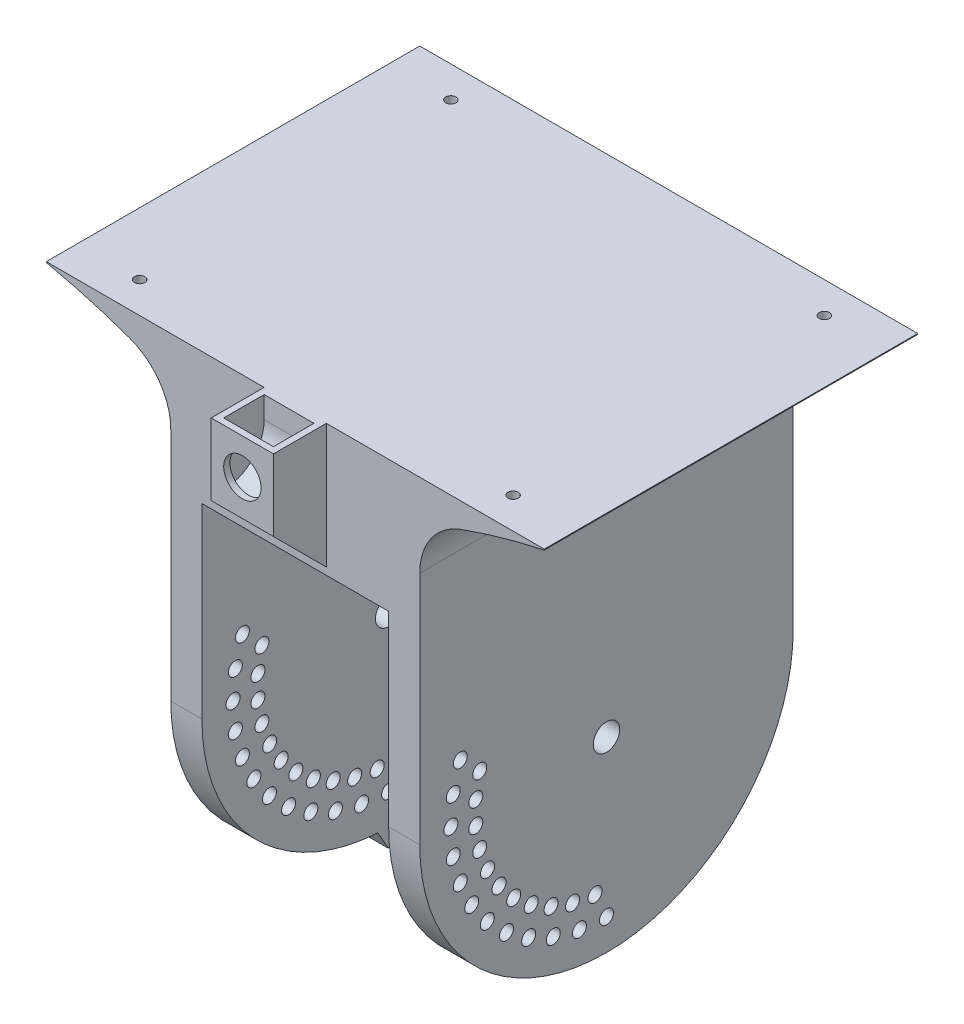
SolidWorks part; units mm, degrees
other "Markup1"
sketch "Sketch9" plane through (-80, -368.8034, 17) normal (-0.4093, -0.7365, 0.5387) x (-0.0783, -0.5598, -0.8249)
ref_plane "Front Plane" through (0, 0, 0) normal (0, 0, 1) x (1, 0, 0)
ref_plane "Top Plane" through (0, 0, 0) normal (0, 1, 0) x (1, 0, 0)
ref_plane "Right Plane" through (0, 0, 0) normal (1, 0, 0) x (0, 0, -1)
sketch "Sketch1" plane through (0, 0, 0) normal (0, 0, 1) x (1, 0, 0)
  line L0 (-10, -206.5) -> (-80, -206.5) construction
  line L1 (-10, -206.5) -> (-80, -206.5)
  line L2 (80, -206.5) -> (-80, -206.5) construction
  line L3 (80, -206.5) -> (-80, -206.5)
  line L4 (80, -206.5) -> (80, -206.7712)
  line L5 (-80, -206.5) -> (-80, -206.7712)
  arc A0 (80.2, -206.7286) -> (225.2451, -153.1407) centre (-32.1304, 320.4019) ccw construction
  arc A1 (80.2, -206.7286) -> (225.2451, -153.1407) centre (-32.1304, 320.4019) ccw
  arc A2 (-225.2451, -153.1407) -> (-80.2, -206.7286) centre (32.1304, 320.4019) ccw construction
  arc A3 (-225.2451, -153.1407) -> (-80.2, -206.7286) centre (32.1304, 320.4019) ccw
  arc A4 (80.2, -206.7286) -> (-80.2, -206.7286) centre (0, 169.6244) cw construction
  arc A5 (-80, -206.7712) -> (80, -206.7712) centre (0, 169.6244) ccw construction
  arc A6 (-80, -206.7712) -> (-51.0096, -215.1963) centre (-122.7938, -408.1138) cw
  arc A7 (80, -206.7712) -> (51.0096, -215.1963) centre (122.7938, -408.1138) ccw
  arc A8 (51.0096, -215.1963) -> (-51.0096, -215.1963) centre (0, -78.1099) cw
  point P13 (-51.0096, -215.1963)
  point P20 (0, 0)
  point P21 (0, 0)
  point P22 (0, 0)
  point P23 (-68.6071, -211.6046)
extrude "Boss-Extrude1" add sketch "Sketch1" against normal up to surface (120 mm away) contours L5 A5 L4 L3 L1 region at (0, -213.5137, 0)
sketch "Sketch2" plane through (0, 0, -120) normal (0, 0, -1) x (-1, 0, 0)
  line L1 (-40, -218.8034) -> (40, -218.8034)
  line L2 (-40, -218.8034) -> (-40, -248.8034)
  line L3 (-40, -248.8034) -> (40, -248.8034)
  line L4 (40, -218.8034) -> (40, -248.8034)
  arc A1 (-51.0096, -215.1963) -> (51.0096, -215.1963) centre (0, -78.1099) ccw construction
  point P4 (0, 0)
  point P7 (0, 0)
  point P8 (46.2922, -257.5156)
  point P9 (0, 0)
  point P13 (0, 0)
  dimension "D1" = 30
  dimension "D2" = 80
extrude "Boss-Extrude2" add sketch "Sketch2" against normal up to surface (120 mm away) up to face at (0, -210.8422, 0)
fillet "Fillet1" radius 20 2 edges at (40, -218.8034, -60) (-40, -218.8034, -60)
sketch "Sketch3" plane through (0, -248.8034, 0) normal (0, -1, 0) x (1, 0, 0)
  line L0 (40, -120) -> (-40, -120) construction
  line L1 (40, 0) -> (30, 0)
  line L2 (40, 0) -> (40, -120)
  line L3 (40, -120) -> (30, -120)
  line L4 (30, 0) -> (30, -120)
  line L5 (40, 0) -> (-40, 0) construction
  line L6 (-40, -120) -> (-30, -120)
  line L7 (-40, -120) -> (-40, 0)
  line L8 (-40, 0) -> (-30, 0)
  line L9 (-30, -120) -> (-30, 0)
  dimension "D1" = 10
extrude "Boss-Extrude3" add sketch "Sketch3" along normal blind 120
fillet "Fillet2" radius 60 4 edges at (35, -368.8034, -120) (35, -368.8034, 0) (-35, -368.8034, 0) (-35, -368.8034, -120)
sketch "Sketch4" plane through (-40, 0, 0) normal (-1, 0, 0) x (0, 0, 1)
  line L0 (-60, -308.8034) -> (-60, -358.8034) construction
  line L1 (-60, -308.8034) -> (-60, -358.8034) construction
  line L2 (-60, -308.8034) -> (-51.3176, -358.0437) construction
  line L3 (-60, -308.8034) -> (-56.3255, -350.8034) construction
  line L4 (-60, -308.8034) -> (-56.3255, -350.8034) construction
  line L5 (-60, -308.8034) -> (-49.0881, -349.5272) construction
  circle A0 centre (-60, -308.8034) radius 4.25
  circle A1 centre (-60, -358.8034) radius 2.25
  circle A2 centre (-51.3176, -358.0437) radius 2.25
  circle A3 centre (-42.899, -355.788) radius 2.25
  circle A4 centre (-35, -352.1046) radius 2.25
  circle A5 centre (-27.8606, -347.1056) radius 2.25
  circle A6 centre (-21.6978, -340.9427) radius 2.25
  circle A7 centre (-16.6987, -333.8034) radius 2.25
  circle A8 centre (-13.0154, -325.9044) radius 2.25
  circle A9 centre (-10.7596, -317.4858) radius 2.25
  circle A10 centre (-10, -308.8034) radius 2.25
  circle A11 centre (-10.7596, -300.1209) radius 2.25
  circle A12 centre (-13.0154, -291.7023) radius 2.25
  circle A13 centre (-56.3255, -350.8034) radius 2.25
  circle A14 centre (-49.0881, -349.5272) radius 2.25
  circle A15 centre (-42.1822, -347.0137) radius 2.25
  circle A16 centre (-35.8178, -343.3392) radius 2.25
  circle A17 centre (-30.1881, -338.6153) radius 2.25
  circle A18 centre (-25.4642, -332.9856) radius 2.25
  circle A19 centre (-21.7897, -326.6211) radius 2.25
  circle A20 centre (-19.2761, -319.7153) radius 2.25
  circle A21 centre (-18, -312.4779) radius 2.25
  circle A22 centre (-18, -305.1288) radius 2.25
  circle A23 centre (-19.2761, -297.8914) radius 2.25
  dimension "D1" = 8.5
  dimension "D2" = 4.5
  dimension "D3" = 50
  dimension "D5" = 10
  dimension "D6" = 5
  dimension "D7" = 42
  dimension "D9" = 10
  dimension "D4" = 12
  dimension "D8" = 11
extrude "Cut-Extrude1" cut sketch "Sketch4" against normal through all
ref_plane "Plane1" through (-10, -206.5, 0) normal (0, 0, -1) x (-1, 0, 0)
sketch "Sketch6" plane through (0, -206.5, 0) normal (0, 1, 0) x (1, 0, 0)
  line L0 (10, -17) -> (10, 0) construction
  line L1 (10, -17) -> (10, 0)
  line L2 (-10, -17) -> (-10, 0) construction
  line L3 (-10, -17) -> (10, -17) construction
  line L4 (80, 120) -> (-80, 120)
  line L5 (-80, 120) -> (-80, 0)
  line L6 (-80, 0) -> (80, 0)
  line L7 (80, 0) -> (80, 120)
  line L10 (-10, 0) -> (10, 0)
  line L12 (-10, -17) -> (-10, 0)
  line L13 (-10, -17) -> (10, -17)
  line L14 (8, -15) -> (-8, -15) construction
  line L15 (-8, -15) -> (-8, -2) construction
  line L16 (-8, -2) -> (8, -2) construction
  line L17 (8, -2) -> (8, -15) construction
  line L18 (8, -15) -> (-8, -15)
  line L19 (-8, -15) -> (-8, -2)
  line L20 (-8, -2) -> (8, -2)
  line L21 (8, -2) -> (8, -15)
  dimension "D1" = 0
extrude "Boss-Extrude4" add sketch "Sketch6" against normal blind 20
sketch "Sketch7" plane through (0, -226.5, 0) normal (0, -1, 0) x (1, 0, 0)
  line L4 (10, 17) -> (-10, 17)
  line L5 (-10, 17) -> (-10, 0)
  line L6 (-10, 0) -> (10, 0)
  line L7 (10, 0) -> (10, 17)
  line L8 (10, 17) -> (-10, 17)
  line L9 (-10, 17) -> (-10, 0)
  line L10 (-10, 0) -> (10, 0)
  line L11 (10, 0) -> (10, 17)
  dimension "D1" = 0
extrude "Boss-Extrude5" add sketch "Sketch7" along normal blind 3
fillet "Fillet3" radius 13 1 edges at (0, -226.5, 2)
sketch "Sketch8" plane through (0, 0, 17) normal (0, 0, 1) x (1, 0, 0)
  line L0 (0, -206.5) -> (0, -229.5) construction
  line L1 (-10, -206.5) -> (10, -206.5) construction
  line L2 (10, -229.5) -> (-10, -229.5) construction
  circle A0 centre (0, -218) radius 6
  point P8 (0, 0)
  dimension "D1" = 12
extrude "Cut-Extrude2" cut sketch "Sketch8" against normal blind 3
chamfer "Chamfer1" distance 17 angle 45 1 edges at (0, -229.5, 0)
sketch "Sketch10" plane through (0, -206.5, 0) normal (0, 1, 0) x (1, 0, 0)
  line L0 (0, 120) -> (0, 0) construction
  line L1 (-80, 120) -> (80, 120) construction
  line L2 (-10, 0) -> (-80, 0) construction
  line L4 (60, 10) -> (-60, 10) construction
  line L5 (60, 10) -> (60, 110) construction
  line L6 (60, 110) -> (-60, 110) construction
  line L7 (-60, 10) -> (-60, 110) construction
  line L8 (60, 10) -> (-60, 110) construction
  line L9 (60, 110) -> (-60, 10) construction
  circle A0 centre (-60, 110) radius 1.65
  circle A1 centre (-60, 10) radius 1.65
  circle A2 centre (60, 10) radius 1.65
  circle A3 centre (60, 110) radius 1.65
  point P9 (0, 60)
  dimension "D3" = 3.3
  dimension "D1" = 100
  dimension "D2" = 120
extrude "Cut-Extrude3" cut sketch "Sketch10" against normal through all
ref_plane "Plane2" through (0, -210.5, 0) normal (0, 1, 0) x (1, 0, 0)
sketch "Sketch11" plane through (0, -210.5, 0) normal (0, 1, 0) x (1, 0, 0)
  circle A0 centre (-60, 110) radius 3
  circle A1 centre (-60, 10) radius 3
  circle A2 centre (60, 110) radius 3
  circle A3 centre (60, 10) radius 3
  dimension "D1" = 6
extrude "Cut-Extrude4" cut sketch "Sketch11" against normal through all
sketch "Sketch13" plane through (-40, 0, 0) normal (-1, 0, 0) x (0, 0, 1)
  line L0 (-60, -1308.8034) -> (-60, 48691.1966) construction
  line L1 (-60, -374.8034) -> (-63.5153, -368.7003)
  line L2 (-63.5153, -368.7003) -> (-60, -366.6755)
  line L3 (-56.4847, -368.7003) -> (-60, -366.6755)
  line L4 (-60, -374.8034) -> (-56.4847, -368.7003)
  arc A0 (-120, -308.8034) -> (-60, -368.8034) centre (-60, -308.8034) ccw construction
  dimension "D1" = 6
extrude "Boss-Extrude6" add sketch "Sketch13" against normal up to surface (10 mm away) up to face at (-30, -325.9044, -10.7654)
